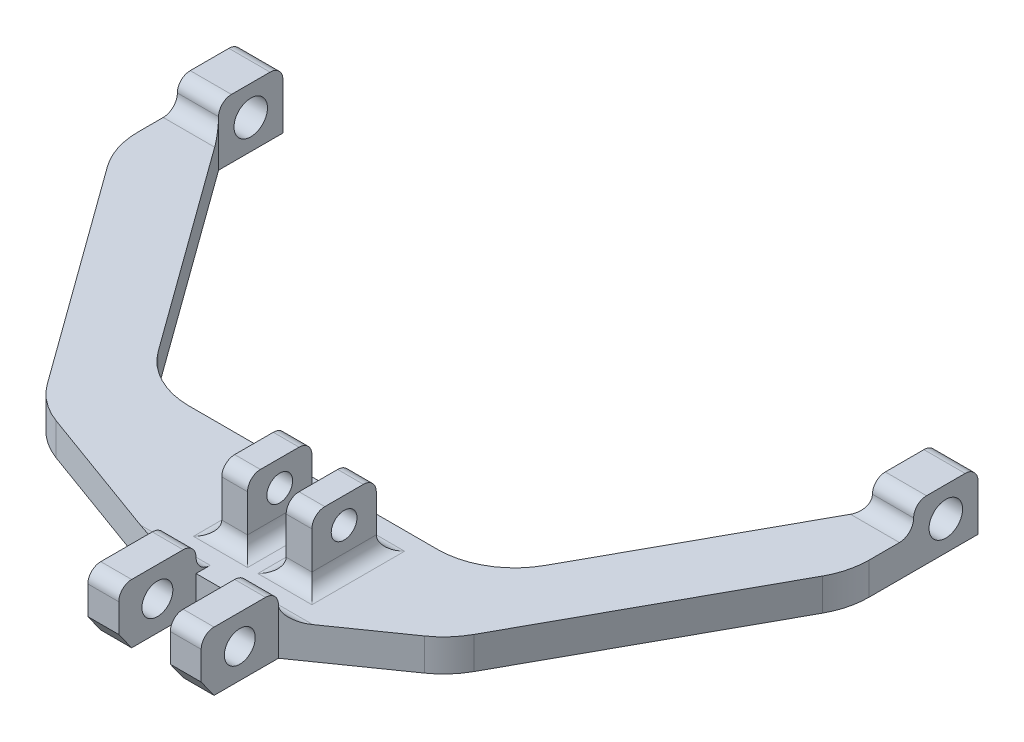
SolidWorks part; units mm, degrees
material "AISI 4130 Steel, annealed at 865C"
ref_plane "Front Plane" through (0, 0, 0) normal (0, 0, 1) x (1, 0, 0)
ref_plane "Top Plane" through (0, 0, 0) normal (0, 1, 0) x (1, 0, 0)
ref_plane "Right Plane" through (0, 0, 0) normal (1, 0, 0) x (0, 0, -1)
sketch "Sketch2" plane through (0, 0, 0) normal (0, 1, 0) x (1, 0, 0)
  line L1 (72.5775, -150.1384) -> (147.7529, -177.5)
  line L2 (147.7529, -177.5) -> (147.7529, -207.5)
  line L3 (147.7529, -207.5) -> (159.7529, -207.5)
  line L4 (159.7529, -207.5) -> (159.7529, -177.5)
  line L5 (159.7529, -177.5) -> (169.7529, -177.5)
  line L6 (169.7529, -177.5) -> (179.7529, -177.5)
  line L9 (179.7529, -177.5) -> (179.7529, -207.5)
  line L10 (179.7529, -207.5) -> (191.7529, -207.5)
  line L11 (191.7529, -207.5) -> (191.7529, -177.5)
  line L12 (191.7529, -177.5) -> (230.8293, -150.1384)
  line L14 (86.6653, -122.5) -> (216.2808, -122.5)
  line L18 (0, -50) -> (72.5775, -150.1384)
  line L20 (16, -25) -> (86.6653, -122.5)
  line L23 (269.9194, -25) -> (216.2808, -122.5)
  line L24 (285.9194, -50) -> (230.8293, -150.1384)
  line L28 (285.9194, 0) -> (285.9194, -50)
  line L34 (0, 0) -> (16, 0)
  line L35 (16, 0) -> (16, -25)
  line L36 (269.9194, -25) -> (269.9194, 0)
  line L37 (269.9194, 0) -> (285.9194, 0)
  line L39 (0, 0) -> (0, -50)
  point P0 (8, 0)
  point P2 (169.7529, -192.5)
  point P3 (8, -12.5)
  point P9 (277.9194, -12.5)
  point P16 (159.7529, -192.5)
  point P29 (277.9194, 0)
  point P30 (16, -12.5)
  dimension "D3" = 30
  dimension "D4" = 12
  dimension "D9" = 10
  dimension "D6" = 145
  dimension "D5" = 80
  dimension "D8" = 160
  dimension "D18" = 25
  dimension "D7" = 25
  dimension "D13" = 16
  dimension "D2" = 55
  dimension "D12" = 180
  dimension "D10" = 242
  dimension "D11" = 210
extrude "Boss-Extrude1" add sketch "Sketch2" along normal blind 12.5
sketch "Sketch5" plane through (0, 12.5, 0) normal (0, 1, 0) x (1, 0, 0)
  line L0 (159.7529, -207.5) -> (159.7529, -177.5) construction
  line L1 (152.2529, -135) -> (162.2529, -135)
  line L2 (152.2529, -135) -> (152.2529, -160)
  line L3 (152.2529, -160) -> (162.2529, -160)
  line L4 (162.2529, -135) -> (162.2529, -160)
  line L5 (177.2529, -135) -> (187.2529, -135)
  line L6 (177.2529, -135) -> (177.2529, -160)
  line L7 (177.2529, -160) -> (187.2529, -160)
  line L8 (187.2529, -135) -> (187.2529, -160)
  line L9 (162.2529, -147.5) -> (177.2529, -147.5) construction
  line L10 (159.7529, -192.5) -> (179.7529, -192.5) construction
  line L11 (179.7529, -177.5) -> (179.7529, -207.5) construction
  point P10 (159.7529, -192.5)
  point P11 (162.2529, -147.5)
  point P18 (169.7529, -192.5)
  point P19 (169.7529, -147.5)
  dimension "D1" = 45
  dimension "D2" = 10
  dimension "D3" = 25
  dimension "D4" = 15
extrude "Boss-Extrude2" add sketch "Sketch5" along normal blind 25
sketch "Sketch7" plane through (0, 12.5, 0) normal (0, 1, 0) x (1, 0, 0)
  line L1 (147.7529, -207.5) -> (159.7529, -207.5)
  line L2 (147.7529, -207.5) -> (147.7529, -177.5)
  line L3 (147.7529, -177.5) -> (159.7529, -177.5)
  line L4 (159.7529, -207.5) -> (159.7529, -177.5)
  line L5 (179.7529, -207.5) -> (191.7529, -207.5)
  line L6 (179.7529, -207.5) -> (179.7529, -177.5)
  line L7 (179.7529, -177.5) -> (191.7529, -177.5)
  line L8 (191.7529, -207.5) -> (191.7529, -177.5)
extrude "Boss-Extrude4" add sketch "Sketch7" along normal blind 10.5
sketch "Sketch8" plane through (147.7529, 0, 0) normal (-1, 0, 0) x (0, 0, 1)
  line L0 (177.5, 23) -> (207.5, 23) construction
  line L1 (207.5, 23) -> (207.5, 0) construction
  circle A0 centre (192.5, 11.5) radius 6
  point P4 (192.5, 23)
  point P7 (207.5, 11.5)
  dimension "D1" = 12
extrude "Cut-Extrude1" cut sketch "Sketch8" against normal through all
sketch "Sketch11" plane through (0, 12.5, 0) normal (0, 1, 0) x (1, 0, 0)
  line L0 (285.9194, -50) -> (285.9194, 0) construction
  line L1 (0, 0) -> (16, 0)
  line L2 (0, 0) -> (0, -25)
  line L3 (0, -25) -> (16, -25)
  line L4 (16, 0) -> (16, -25)
  line L5 (269.9194, 0) -> (285.9194, 0)
  line L6 (269.9194, 0) -> (269.9194, -25)
  line L7 (269.9194, -25) -> (285.9194, -25)
  line L8 (285.9194, 0) -> (285.9194, -25)
extrude "Boss-Extrude6" add sketch "Sketch11" along normal blind 10.5
sketch "Sketch12" plane through (0, 0, 0) normal (-1, 0, 0) x (0, 0, 1)
  line L0 (0, 23) -> (25, 23) construction
  line L1 (0, 0) -> (50, 0) construction
  circle A0 centre (12.5, 11.5) radius 6.5
  point P5 (12.5, 23)
  dimension "D1" = 13
  dimension "D2" = 11.5
extrude "Cut-Extrude3" cut sketch "Sketch12" against normal through all
sketch "Sketch13" plane through (152.2529, 0, 0) normal (-1, 0, 0) x (0, 0, 1)
  line L0 (50, 12.5) -> (150.1384, 12.5) construction
  line L1 (135, 37.5) -> (160, 37.5) construction
  circle A0 centre (147.5, 27.5) radius 5
  point P7 (147.5, 37.5)
  dimension "D1" = 10
  dimension "D2" = 15
extrude "Cut-Extrude4" cut sketch "Sketch13" against normal through all
fillet "Fillet2" radius 30 6 edges at (285.9194, 6.25, 50) (230.8293, 6.25, 150.1384) (216.2808, 6.25, 122.5) (86.6653, 6.25, 122.5) (72.5775, 6.25, 150.1384) (0, 6.25, 50)
fillet "Fillet3" radius 5 12 edges at (185.7529, 23, 207.5) (153.7529, 23, 207.5) (185.7529, 23, 177.5) (153.7529, 23, 177.5) (157.2529, 37.5, 135) (157.2529, 37.5, 160) (182.2529, 37.5, 135) (182.2529, 37.5, 160) (277.9194, 23, 0) (277.9194, 23, 25) (8, 23, 0) (8, 23, 25)
fillet "Fillet4" radius 5.5 12 edges at (153.7529, 12.5, 177.5) (185.7529, 12.5, 177.5) (182.2529, 12.5, 135) (157.2529, 12.5, 135) (182.2529, 12.5, 160) (157.2529, 12.5, 160) (8, 12.5, 25) (277.9194, 12.5, 25) (152.2529, 12.5, 147.5) (187.2529, 12.5, 147.5) (177.2529, 12.5, 147.5) (162.2529, 12.5, 147.5)
chamfer "Chamfer1" distance 5 distance2 7 2 edges at (185.7529, 0, 207.5) (153.7529, 0, 207.5) first distance on face at (153.8575, 0, 109.6991)
sketch "Sketch14" plane through (147.7529, 0, 0) normal (-1, 0, 0) x (0, 0, 1)
  line L0 (192.5, 11.5) -> (206.0443, 21.6105) construction
  line L1 (200.989, 28.3827) -> (211.0995, 14.8384) construction
  circle A1 centre (192.5, 11.5) radius 6 construction
  arc A2 (207.5, 18) -> (202.5, 23) centre (202.5, 18) ccw construction
  point P7 (206.0443, 21.6105)
  point P10 (0, 0)
  dimension "D1" = 16.9018
equation "\"LCA Rear\"= 210"
equation "\"UCA Front\"= 242"
equation "\"UCA out\"= 180"
equation "\"D12@Sketch2\"=\"UCA out\""
equation "\"D10@Sketch2\"=\"UCA Front\""
equation "\"D11@Sketch2\"=\"LCA Rear\""
